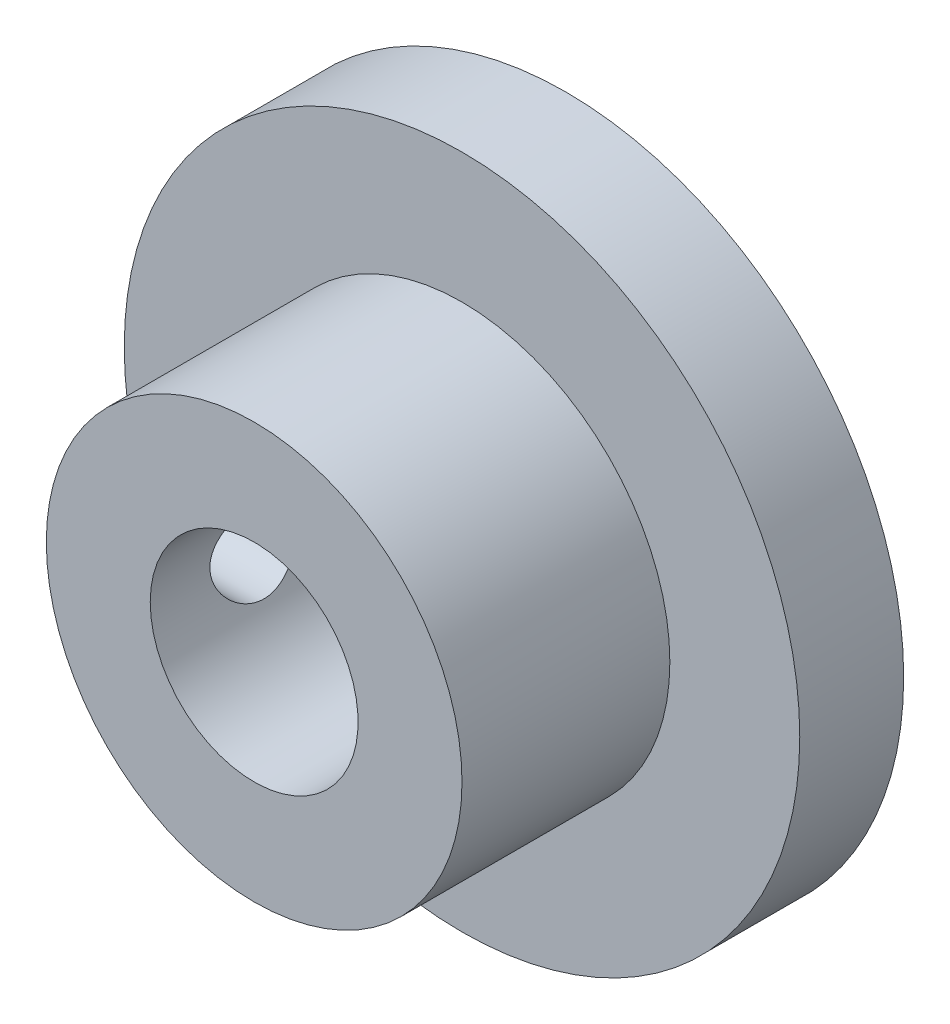
SolidWorks part; units mm, degrees
material "303 Stainless"
ref_plane "Front Plane" through (0, 0, 0) normal (0, 0, 1) x (1, 0, 0)
ref_plane "Top Plane" through (0, 0, 0) normal (0, 1, 0) x (1, 0, 0)
ref_plane "Right Plane" through (0, 0, 0) normal (1, 0, 0) x (0, 0, -1)
sketch "Sketch1" plane through (0, 0, 0) normal (0, 0, 1) x (1, 0, 0)
  circle A0 centre (0, 0) radius 10.3187
  dimension "D1" = 20.6375
extrude "Boss-Extrude1" add sketch "Sketch1" along normal blind 3.175
sketch "Sketch2" plane through (0, 0, 3.175) normal (0, 0, 1) x (1, 0, 0)
  circle A0 centre (0, 0) radius 6.35
  dimension "D1" = 12.7
extrude "Boss-Extrude2" add sketch "Sketch2" along normal blind 6.35
sketch "Sketch3" plane through (0, 0, 0) normal (0, 0, -1) x (-1, 0, 0)
  circle A0 centre (0, 0) radius 3.175
  dimension "D1" = 6.35
extrude "Cut-Extrude1" cut sketch "Sketch3" against normal through all
ref_plane "Plane1" through (-6.35, 0, 0) normal (-1, 0, 0) x (0, 0, 1)
hole_wizard "#6-32 Tapped Hole1" positions "Sketch4" profile "Sketch5" tap size "#6-32" standard "ANSI Inch" end condition up to next
sketch "Sketch4" plane through (-6.35, 0, 0) normal (-1, 0, 0) x (0, 0, 1)
  line L0 (9.525, -6.35) -> (9.525, 6.35) construction
  line L1 (9.525, -6.35) -> (9.525, 6.35) construction
  line L2 (3.175, -10.3187) -> (3.175, 10.3187) construction
  line L3 (3.175, -10.3187) -> (3.175, 10.3187) construction
  line L4 (9.525, 0) -> (3.175, 0) construction
  point P0 (6.35, 0)
sketch "Sketch5" plane through (-6.35, 0, 6.35) normal (0, 1, 0) x (0, 0, 1)
  line L0 (0, 0) -> (0, 3.175)
  line L1 (0, 3.175) -> (1.3525, 3.175)
  line L2 (1.3525, 3.175) -> (1.3525, 0)
  line L5 (1.3525, 0) -> (0, 0)
  line L11 (0, -6.35) -> (0, 107.95) construction
  dimension "Thru Tap Drill Dia." = 2.7051
  dimension "Thru Tap Drill Depth" = 3.175
cosmetic thread "Hole Thread1" parameters "D2"=3.5052
equation "\"hub\"= .5"
equation "\"bore\"= .25"
equation "\"hub l\"= .25"
equation "\"pitch\"= .8125"
equation "\"D1@Sketch1\"=\"pitch\""
equation "\"D1@Sketch2\"=\"hub\""
equation "\"D1@Sketch3\"=\"bore\""
equation "\"face\"= .125"
equation "\"D1@Boss-Extrude1\"=\"face\""
equation "\"D1@Boss-Extrude2\"=\"hub l\""
